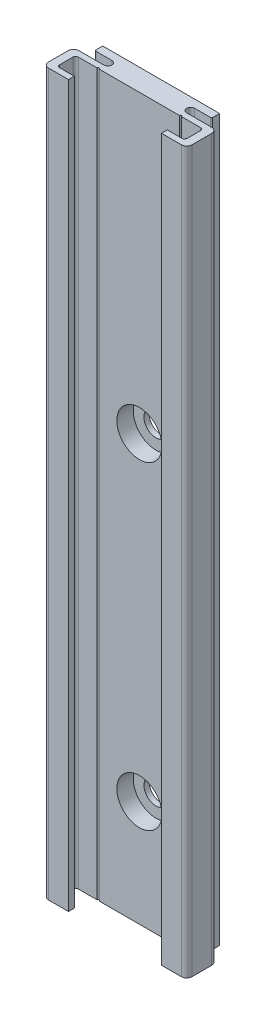
SolidWorks part; units mm, degrees
material "AISI 1035 Acier (SS)"
ref_plane "Plan de face" through (0, 0, 0) normal (0, 0, 1) x (1, 0, 0)
ref_plane "Plan de dessus" through (0, 0, 0) normal (0, 1, 0) x (1, 0, 0)
ref_plane "Plan de droite" through (0, 0, 0) normal (1, 0, 0) x (0, 0, -1)
ref_plane "Plan1" through (0, 0, 0) normal (0, -1, 0) x (1, 0, 0)
sketch "Esquisse1" plane through (0, 0, 0) normal (0, -1, 0) x (1, 0, 0)
  line L0 (13.5, 8.7) -> (-13.5, 8.7)
  line L1 (-13.5, 8.7) -> (-13.5, 3)
  line L2 (-13.5, 3) -> (-7.8, 3)
  line L3 (-7.8, 1.5) -> (-11, 1.5)
  line L4 (-11, 1.5) -> (-11, 0)
  line L5 (-11, 0) -> (11, 0)
  line L6 (11, 0) -> (11, 1.5)
  line L7 (11, 1.5) -> (7.8, 1.5)
  line L8 (7.8, 3) -> (13.5, 3)
  line L9 (13.5, 3) -> (13.5, 8.7)
  arc A0 (-7.8, 3) -> (-7.8, 1.5) centre (-7.8, 2.25) cw
  arc A1 (7.8, 1.5) -> (7.8, 3) centre (7.8, 2.25) cw
extrude "Boss.-Extru.1" add sketch "Esquisse1" against normal blind 1000
sketch "Esquisse2" plane through (0, 1000, 0) normal (0, 1, 0) x (-1, 0, 0)
  line L0 (8.75, 8.7) -> (-8.75, 8.7)
  line L1 (-8.75, 8.7) -> (-8.75, 7.6)
  line L2 (-8.75, 7.6) -> (-12, 7.6)
  line L3 (-12, 7.6) -> (-12, 4.1)
  line L4 (-12, 4.1) -> (12, 4.1)
  line L5 (12, 4.1) -> (12, 7.6)
  line L6 (12, 7.6) -> (8.75, 7.6)
  line L7 (8.75, 7.6) -> (8.75, 8.7)
extrude "Enlèv. mat.-Extru.1" cut sketch "Esquisse2" against normal through all
hole_wizard "Chambrage pour vis à tête hexagonale M41" positions "Esquisse4" profile "Esquisse3" counterbore size "M4" standard "Ansi Metric"
sketch "Esquisse4" plane through (0, 0, 4.1) normal (0, 0, 1) x (1, 0, 0)
  point P0 (0, 980)
  point P1 (0, 920)
  point P2 (0, 860)
  point P3 (0, 800)
  point P4 (0, 740)
  point P5 (0, 680)
  point P6 (0, 620)
  point P7 (0, 560)
  point P8 (0, 500)
  point P9 (0, 440)
  point P10 (0, 380)
  point P11 (0, 320)
  point P12 (0, 260)
  point P13 (0, 200)
  point P14 (0, 140)
  point P15 (0, 80)
  point P16 (0, 20)
sketch "Esquisse3" plane through (0, 980, 4.1) normal (1, 0, 0) x (0, -1, 0)
  line L0 (0, 0) -> (0, 4.1)
  line L1 (0, 4.1) -> (2.25, 4.1)
  line L3 (2.25, 4.1) -> (2.25, 3.1)
  line L4 (2.25, 3.1) -> (4.25, 3.1)
  line L5 (4.25, 3.1) -> (4.25, 0)
  line L7 (4.25, 0) -> (0, 0)
  line L11 (0, -6.35) -> (0, 107.95) construction
  dimension "Diamètre du perçage jusqu'au prochain" = 4.5
  dimension "Profondeur du perçage jusqu'au prochain" = 4.1
  dimension "Diamètre du chambrage" = 8.5
  dimension "Profondeur du chambrage" = 3.1
hole_wizard "Diamètre du perçage Ø0.4 (0.4)1" positions "Esquisse6" profile "Esquisse5" hole size "Ø0.4" standard "Ansi Metric"
sketch "Esquisse6" plane through (0, 0, 0) normal (0, -1, 0) x (-1, 0, 0)
  point P0 (7.75, -4.1)
  point P1 (-7.75, -4.1)
sketch "Esquisse5" plane through (-7.75, 0, 4.1) normal (1, 0, 0) x (0, 0, -1)
  line L0 (0, 0) -> (0, 1000)
  line L1 (0, 1000) -> (0.2, 1000)
  line L2 (0.2, 1000) -> (0.2, 0)
  line L5 (0.2, 0) -> (0, 0)
  line L11 (0, -6.35) -> (0, 107.95) construction
  dimension "Diamètre du perçage jusqu'au prochain" = 0.4
  dimension "Profondeur du perçage jusqu'au prochain" = 1000
fillet "Congé1" radius 0.2 2 edges at (11, 500, 1.5) (-11, 500, 1.5) tangent propagation no
fillet "Congé2" radius 0.5 4 edges at (12, 500, 7.6) (12, 500, 4.1) (-12, 500, 7.6) (-12, 500, 4.1) tangent propagation no
fillet "Congé3" radius 1 4 edges at (13.5, 500, 3) (13.5, 500, 8.7) (-13.5, 500, 3) (-13.5, 500, 8.7) tangent propagation no
sketch "Esquisse9" plane through (0, 0, 0) normal (0, 0, 1) x (1, 0, 0)
  line L0 (-13.5, 0) -> (-13.5, 1000) construction
  line L1 (-13.5, 135.62) -> (13.5, 135.62)
  line L2 (-13.5, 135.62) -> (-13.5, 1000)
  line L3 (-13.5, 1000) -> (13.5, 1000)
  line L4 (13.5, 135.62) -> (13.5, 1000)
  line L5 (13.5, 1000) -> (13.5, 0) construction
  line L6 (7.55, 1000) -> (-7.55, 1000) construction
  dimension "D1" = 135.62
extrude "Enlèv. mat.-Extru.2" cut sketch "Esquisse9" against normal through all both and the other way through all
